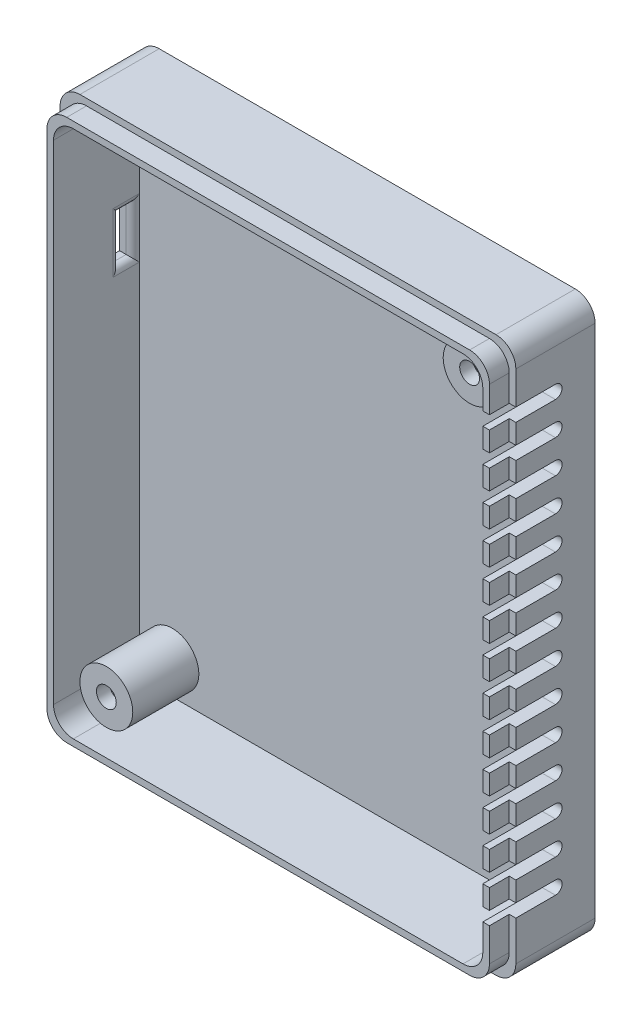
SolidWorks part; units mm, degrees
ref_plane "Front Plane" through (0, 0, 0) normal (0, 0, 1) x (1, 0, 0)
ref_plane "Top Plane" through (0, 0, 0) normal (0, 1, 0) x (1, 0, 0)
ref_plane "Right Plane" through (0, 0, 0) normal (1, 0, 0) x (0, 0, -1)
sketch "Sketch2" plane through (0, 0, 0) normal (0, 0, 1) x (1, 0, 0)
  line L1 (-32.5, 40) -> (32.5, 40)
  line L2 (-32.5, 40) -> (-32.5, -40)
  line L3 (-32.5, -40) -> (32.5, -40)
  line L4 (32.5, 40) -> (32.5, -40)
  line L5 (-32.5, 40) -> (32.5, -40) construction
  line L6 (-32.5, -40) -> (32.5, 40) construction
  line L7 (-34.5, 42) -> (34.5, 42)
  line L8 (-34.5, 42) -> (-34.5, -42)
  line L9 (-34.5, -42) -> (34.5, -42)
  line L10 (34.5, 42) -> (34.5, -42)
  line L11 (-34.5, 42) -> (34.5, -42) construction
  line L12 (-34.5, -42) -> (34.5, 42) construction
  point P0 (0, 0)
  point P6 (0, 0)
  dimension "D1" = 80
  dimension "D2" = 65
  dimension "D3" = 69
  dimension "D4" = 84
extrude "Boss-Extrude1" add sketch "Sketch2" along normal blind 13
sketch "Sketch3" plane through (0, 0, 13) normal (0, 0, 1) x (1, 0, 0)
  line L1 (-33.5, 41) -> (33.5, 41)
  line L2 (-33.5, 41) -> (-33.5, -41)
  line L3 (-33.5, -41) -> (33.5, -41)
  line L4 (33.5, 41) -> (33.5, -41)
  line L5 (-33.5, 41) -> (33.5, -41) construction
  line L6 (-33.5, -41) -> (33.5, 41) construction
  point P0 (0, 0)
  dimension "D1" = 82
  dimension "D2" = 67
extrude "Cut-Extrude1" cut sketch "Sketch3" against normal blind 3 flip side to cut
sketch "Sketch4" plane through (0, 0, 0) normal (0, 0, -1) x (-1, 0, 0)
  line L1 (-34.5, 42) -> (34.5, 42)
  line L2 (-34.5, 42) -> (-34.5, -42)
  line L3 (-34.5, -42) -> (34.5, -42)
  line L4 (34.5, 42) -> (34.5, -42)
  line L5 (-34.5, 42) -> (34.5, -42) construction
  line L6 (-34.5, -42) -> (34.5, 42) construction
  point P0 (0, 0)
  dimension "D1" = 84
  dimension "D2" = 69
extrude "Boss-Extrude2" add sketch "Sketch4" along normal blind 2
fillet "Fillet1" radius 3 12 edges at (32.5, 40, 6.5) (-32.5, 40, 6.5) (-32.5, -40, 6.5) (32.5, -40, 6.5) (-34.5, -42, 4) (-34.5, 42, 4) (34.5, 42, 4) (34.5, -42, 4) (33.5, 41, 11.5) (-33.5, 41, 11.5) (-33.5, -41, 11.5) (33.5, -41, 11.5)
sketch "Sketch5" plane through (34.5, 0, 0) normal (1, 0, 0) x (0, 0, -1)
  line L0 (-4, -39) -> (-4, -33) construction
  line L1 (-10, -39) -> (2, -39) construction
  line L2 (-4, -33) -> (-13, -33)
  line L3 (-13, -38) -> (-13, 38) construction
  line L4 (-13, -33) -> (-13, -31)
  line L5 (-13, -31) -> (-4, -31)
  arc A0 (-4, -33) -> (-4, -31) centre (-4, -32) ccw
extrude "Cut-Extrude2" cut sketch "Sketch5" against normal blind 3
pattern_linear "LPattern1" count 14 spacing 5 along (0, 1, 0) of "Cut-Extrude2"
sketch "Sketch6" plane through (0, 0, 0) normal (0, 0, 1) x (1, 0, 0)
  line L0 (26.5197, 40) -> (26.5197, 35) construction
  line L1 (29.5, 40) -> (-29.5, 40) construction
  line L2 (32.5, 35) -> (27.5, 35) construction
  line L3 (32.5, 34) -> (32.5, 37) construction
  line L4 (-28.3391, -40) -> (-28.3391, -35) construction
  line L5 (-29.5, -40) -> (29.5, -40) construction
  line L6 (-32.5, -35) -> (-27.5, -35) construction
  line L7 (-32.5, 37) -> (-32.5, -37) construction
  circle A0 centre (27.5, 35) radius 4
  circle A1 centre (-27.5, -35) radius 4
extrude "Boss-Extrude3" add sketch "Sketch6" along normal blind 10
sketch "Sketch7" plane through (0, 0, -2) normal (0, 0, -1) x (-1, 0, 0)
  circle A0 centre (27.5, -35) radius 3
  circle A1 centre (-27.5, 35) radius 3
extrude "Cut-Extrude3" cut sketch "Sketch7" against normal up to next contours A0 | A1 | A1 region at (-27.5, -35, -2) region at (27.5, 35, -2)
fillet "Fillet2" radius 2 2 edges at (24.5, 35, -2) (-30.5, -35, -2)
sketch "Sketch8" plane through (0, 0, 10) normal (0, 0, 1) x (1, 0, 0)
  circle A0 centre (-27.5, -35) radius 4
  circle A1 centre (-27.5, -35) radius 1.5
  circle A2 centre (27.5, 35) radius 4
  circle A3 centre (27.5, 35) radius 1.5
extrude "Boss-Extrude4" add sketch "Sketch8" against normal blind 2
sketch "Sketch10" plane through (-34.5, 0, 0) normal (-1, 0, 0) x (0, 0, 1)
  line L0 (4.3718, -42) -> (4.3718, 19.0152) construction
  line L1 (10, -42) -> (-2, -42) construction
  line L2 (-2, 19.0152) -> (1, 19.0152) construction
  line L3 (1, 15.5152) -> (1, 22.5152)
  line L5 (-2, -39) -> (-2, 39) construction
  line L10 (3, 15.5152) -> (1, 15.5152)
  line L11 (3, 15.5152) -> (3, 22.5152)
  line L12 (3, 22.5152) -> (1, 22.5152)
  point P12 (1, 19.0152)
  point P15 (1, -26.0059)
  point P18 (1, 19.0152)
  point P22 (1, 15.5152)
extrude "Cut-Extrude4" cut sketch "Sketch10" against normal blind 3 contours L10 L3 L12 L11
fillet "Fillet10" radius 1 4 edges at (-32.5, 15.5152, 2) (-32.5, 19.0152, 1) (-32.5, 22.5152, 2) (-32.5, 19.0152, 3)
